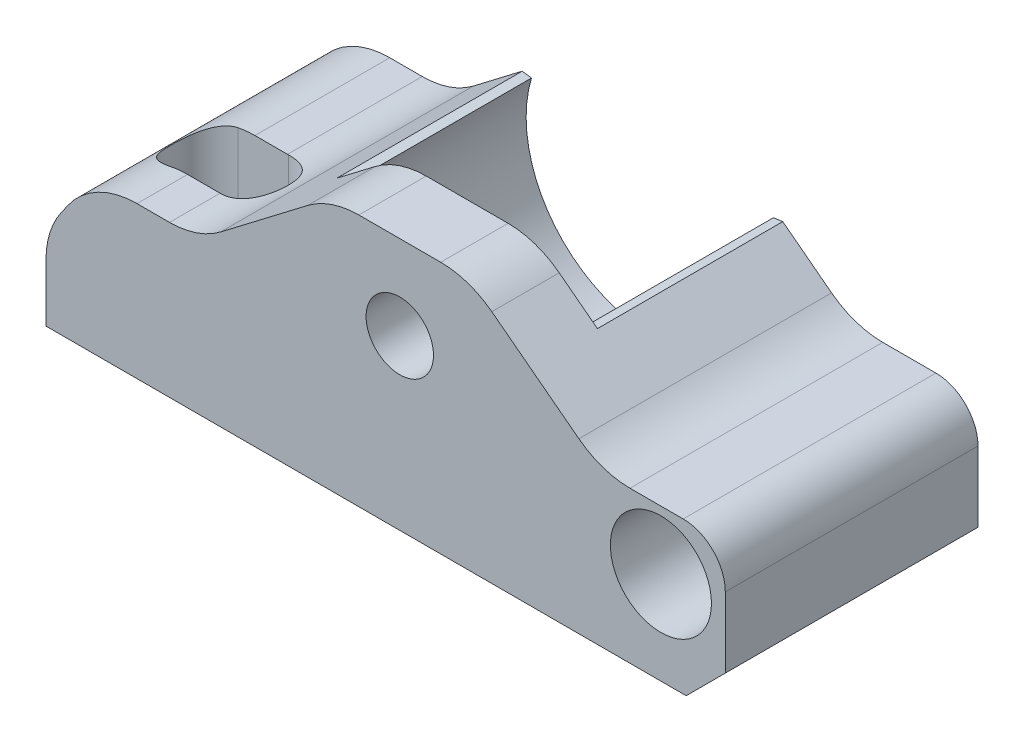
SolidWorks part; units mm, degrees
material "ABS generico"
ref_plane "Piano frontale" through (0, 0, 0) normal (0, 0, 1) x (1, 0, 0)
ref_plane "Piano superiore" through (0, 0, 0) normal (0, 1, 0) x (1, 0, 0)
ref_plane "Piano destro" through (0, 0, 0) normal (1, 0, 0) x (0, 0, -1)
sketch "Schizzo2" plane through (0, 0, 0) normal (0, 0, 1) x (1, 0, 0)
  line L0 (-40, 0) -> (-2, 0)
  line L1 (-40, 0) -> (-40, 9)
  line L2 (-19, 0) -> (-19, 25.5566) construction
  line L3 (-40, 9) -> (-30.9754, 9)
  line L4 (-30.9754, 9) -> (-23.1199, 15)
  line L5 (-23.1199, 15) -> (-14.8801, 15)
  line L6 (-7.0246, 9) -> (-14.8801, 15)
  line L7 (0.3217, 9) -> (-7.0246, 9)
  line L8 (0.3217, 2.3217) -> (-2, 0)
  line L11 (0.3217, 9) -> (0.3217, 2.3217)
  circle A0 centre (-19, 10) radius 2
  circle A1 centre (-3.5, 5.5) radius 1.3432
  point P0 (-40, 0)
  point P1 (2, 0)
  point P10 (-19, 15)
  dimension "D3" = 4
  dimension "D4" = 15
  dimension "D1" = 42
  dimension "D2" = 9
  dimension "D5" = 10
  dimension "D6" = 15.5
  dimension "D7" = 5.5
  dimension "D9" = 4
extrude "Estrusione-Estrusione1" add sketch "Schizzo2" against normal blind 15
sketch "Schizzo3" plane through (0, 0, -15) normal (0, 0, -1) x (-1, 0, 0)
  circle A0 centre (19, 10) radius 7.5
  circle A1 centre (19, 10) radius 2 construction
  dimension "D1" = 15
extrude "Taglio-Estrusione1" cut sketch "Schizzo3" against normal blind 11
chamfer "Smusso3" distance 1 angle 45 2 edges at (-12.0614, 12.8471, -9.5) (-25.9386, 12.8471, -9.5) first distance on face at (-11.322, 12.2824, -6.3333) first distance on face at (-26.678, 12.2824, -6.3333)
fillet "Raccordo1" radius 2.5 1 edges at (0.3217, 9, -7.5)
chamfer "Smusso4" distance 4 angle 35 1 edges at (-40, 9, -7.5) first distance on face at (-40, 4.5, -7.5)
sketch "Schizzo5" plane through (0, 0, 0) normal (0, -1, 0) x (1, 0, 0)
  line L0 (0, -4) -> (39.5666, -4) construction
  line L2 (-35.6119, -5) -> (-32.6119, -5) construction
  line L3 (-40, 0) -> (-2, 0) construction
  line L4 (-35.6119, -3) -> (-32.6119, -3)
  line L5 (-35.6119, -7) -> (-32.6119, -7)
  arc A1 (-35.6119, -3) -> (-35.6119, -7) centre (-35.6119, -5) ccw
  arc A2 (-32.6119, -7) -> (-32.6119, -3) centre (-32.6119, -5) ccw
  point P10 (-34.1119, -5)
  dimension "D2" = 4
  dimension "D4" = 4
  dimension "D5" = 3
extrude "Taglio-Estrusione3" cut sketch "Schizzo5" against normal through all
fillet "Fillet1" radius 5 1 edges at (-7.0246, 9, -7.5)
fillet "Fillet3" radius 5 2 edges at (-40, 5, -7.5) (-37.1992, 9, -1.8916)
fillet "Fillet4" radius 5 2 edges at (-23.1199, 15, -2) (-14.8801, 15, -2)
fillet "Fillet5" radius 5 1 edges at (-30.9754, 9, -1.9251)
sketch "Sketch1" plane through (0, 0, 0) normal (0, 0, 1) x (1, 0, 0)
  circle A0 centre (-3.5, 5.5) radius 3
extrude "Cut-Extrude1" cut sketch "Sketch1" against normal blind 5
